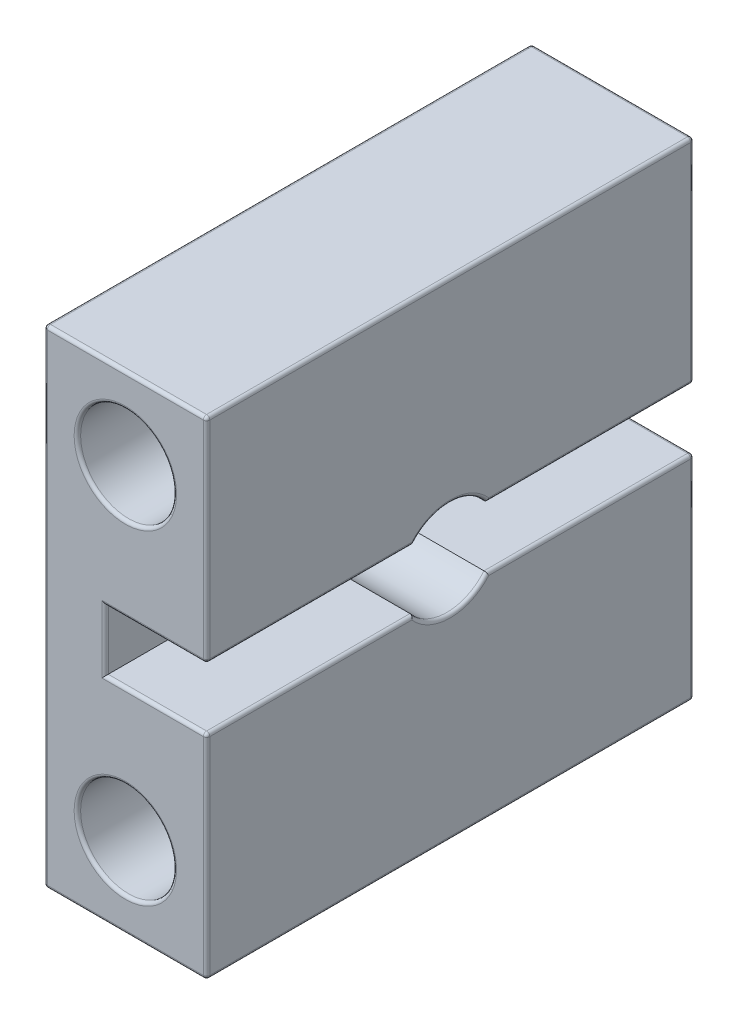
SolidWorks part; units mm, degrees
ref_plane "Front Plane" through (0, 0, 0) normal (0, 0, 1) x (1, 0, 0)
ref_plane "Top Plane" through (0, 0, 0) normal (0, 1, 0) x (1, 0, 0)
ref_plane "Right Plane" through (0, 0, 0) normal (1, 0, 0) x (0, 0, -1)
sketch "Sketch1" plane through (0, 0, 0) normal (0, 0, 1) x (1, 0, 0)
  line L1 (0, 0) -> (25.4, 0)
  line L2 (0, 0) -> (0, 76.2)
  line L3 (0, 76.2) -> (25.4, 76.2)
  line L4 (25.4, 0) -> (25.4, 76.2)
  dimension "D1" = 76.2
  dimension "D2" = 25.4
extrude "Extrude1" add sketch "Sketch1" along normal blind 76.2
hole_wizard "Ø15.0 (15) Diameter Hole1" positions "3DSketch1" profile "Sketch2" hole size "Ø15.0" standard "Ansi Metric" end condition up to next
sketch3d "3DSketch1"
  line L0 (25.4, 76.2, 76.2) -> (0, 76.2, 76.2) construction
  line L1 (0, 76.2, 76.2) -> (0, 0, 76.2) construction
  line L2 (0, 0, 76.2) -> (25.4, 0, 76.2) construction
  point P0 (12.7, 63.5, 76.2)
  point P2 (12.7, 12.7, 76.2)
  dimension "D1" = 12.7
  dimension "D2" = 12.7
  dimension "D3" = 12.7
  dimension "D4" = 12.7
sketch "Sketch2" plane through (12.7, 63.5, 76.2) normal (1, 0, 0) x (0, -1, 0)
  line L0 (0, 0) -> (0, 76.2)
  line L1 (0, 76.2) -> (7.5, 76.2)
  line L2 (7.5, 76.2) -> (7.5, 0)
  line L5 (7.5, 0) -> (0, 0)
  line L11 (0, -6.35) -> (0, 107.95) construction
  dimension "Thru Hole Dia." = 15
  dimension "Thru Hole Depth" = 76.2
sketch "Sketch9" plane through (0, 0, 0) normal (-1, 0, 0) x (0, 0, 1)
  line L0 (0, 76.2) -> (76.2, 0) construction
  circle A0 centre (38.1, 38.1) radius 7.493
  dimension "D1" = 14.986
extrude "Extrude3" cut sketch "Sketch9" against normal up to next
sketch "Sketch7" plane through (25.4, 0, 0) normal (1, 0, 0) x (0, 0, -1)
  line L0 (-76.2, 38.1) -> (0, 38.1) construction
  line L1 (-76.2, 0) -> (-76.2, 76.2) construction
  line L2 (0, 0) -> (0, 76.2) construction
  line L3 (-76.2, 33.3375) -> (0, 33.3375)
  line L4 (-76.2, 42.8625) -> (0, 42.8625)
  line L5 (0, 33.3375) -> (0, 42.8625)
  line L6 (-76.2, 33.3375) -> (-76.2, 42.8625)
  dimension "D1" = 4.7625
  dimension "D2" = 4.7625
extrude "Extrude2" cut sketch "Sketch7" against normal blind 15.875
fillet "Fillet1" radius 0.508 31 edges at (5.2, 12.7, 0) (5.2, 63.5, 0) (12.7, 0, 0) (17.4625, 33.3375, 0) (9.525, 38.1, 0) (17.4625, 42.8625, 0) (0, 0, 38.1) (0, 38.1, 0) (0, 76.2, 38.1) (12.7, 76.2, 0) (25.4, 0, 38.1) (25.4, 33.3375, 60.0424) (25.4, 33.3375, 16.1576) (25.4, 16.6687, 0) (25.4, 76.2, 38.1) (25.4, 59.5312, 0) (25.4, 42.8625, 16.1576) (25.4, 42.8625, 60.0424) (17.4625, 33.3375, 76.2) (25.4, 16.6687, 76.2) (12.7, 0, 76.2) (0, 38.1, 76.2) (12.7, 76.2, 76.2) (25.4, 59.5313, 76.2) (17.4625, 42.8625, 76.2) (9.525, 38.1, 76.2) (20.2, 12.7, 76.2) (20.2, 63.5, 76.2) (0, 38.1, 45.593) (25.4, 30.607, 38.1) (25.4, 45.593, 38.1)
